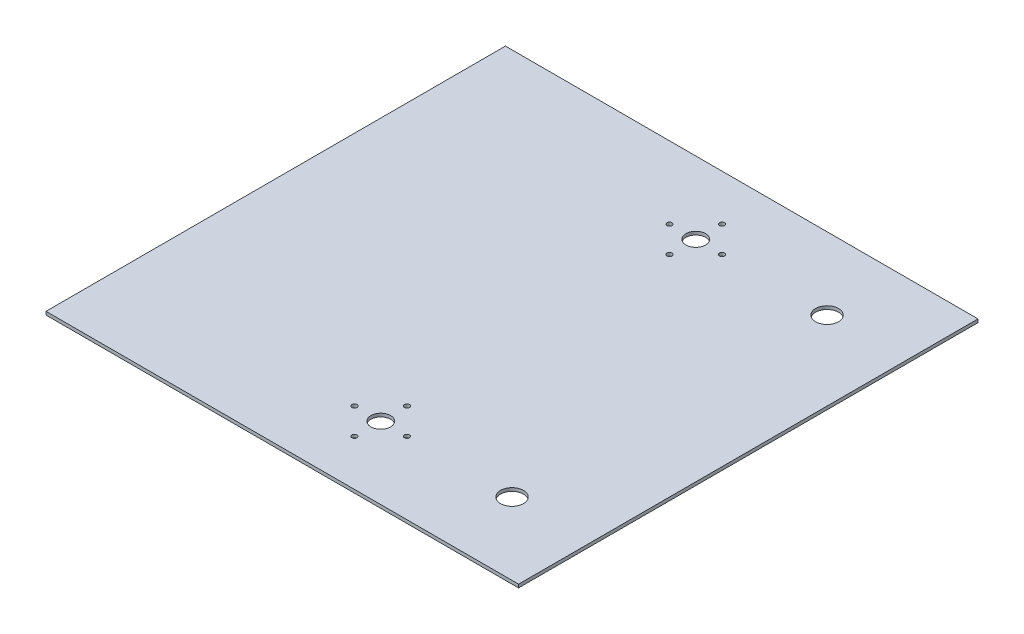
SolidWorks part; units mm, degrees
material "6061 Alloy"
ref_plane "Front Plane" through (0, 0, 0) normal (0, 0, 1) x (1, 0, 0)
ref_plane "Top Plane" through (0, 0, 0) normal (0, 1, 0) x (1, 0, 0)
ref_plane "Right Plane" through (0, 0, 0) normal (1, 0, 0) x (0, 0, -1)
sketch "Sketch1" plane through (0, 0, 0) normal (0, 1, 0) x (1, 0, 0)
  line L1 (228.6, -222.25) -> (-228.6, -222.25)
  line L2 (228.6, -222.25) -> (228.6, 222.25)
  line L3 (228.6, 222.25) -> (-228.6, 222.25)
  line L4 (-228.6, -222.25) -> (-228.6, 222.25)
  line L5 (228.6, -222.25) -> (-228.6, 222.25) construction
  line L6 (228.6, 222.25) -> (-228.6, -222.25) construction
  point P0 (0, 0)
  dimension "D1" = 457.2
  dimension "D2" = 444.5
extrude "Boss-Extrude1" add sketch "Sketch1" along normal blind 3.175
sketch "Sketch3" plane through (0, 3.175, 0) normal (0, 1, 0) x (1, 0, 0)
  arc A0 (34.925, -152.4) -> (15.875, -152.4) centre (25.4, -152.4) ccw construction
  arc A1 (15.875, -152.4) -> (34.925, -152.4) centre (25.4, -152.4) ccw construction
  arc A2 (34.925, -152.4) -> (15.875, -152.4) centre (25.4, -152.4) ccw
  arc A3 (15.875, -152.4) -> (34.925, -152.4) centre (25.4, -152.4) ccw
  arc A4 (34.925, 152.4) -> (15.875, 152.4) centre (25.4, 152.4) ccw construction
  arc A5 (15.875, 152.4) -> (34.925, 152.4) centre (25.4, 152.4) ccw construction
  arc A6 (34.925, 152.4) -> (15.875, 152.4) centre (25.4, 152.4) ccw
  arc A7 (15.875, 152.4) -> (34.925, 152.4) centre (25.4, 152.4) ccw
extrude "Cut-Extrude2" cut sketch "Sketch3" against normal through all
hole_wizard "#10 (0.1935) Diameter Hole1" positions "Sketch4" profile "Sketch5" hole size "#10" standard "ANSI Inch" end condition through all
sketch "Sketch4" plane through (0, 3.175, 0) normal (0, 1, 0) x (1, 0, 0)
  arc A0 (27.4193, -127) -> (23.3807, -127) centre (25.4, -127) ccw construction
  arc A1 (23.3807, -127) -> (27.4193, -127) centre (25.4, -127) ccw construction
  arc A2 (2.0193, -152.4) -> (-2.0193, -152.4) centre (0, -152.4) ccw construction
  arc A3 (-2.0193, -152.4) -> (2.0193, -152.4) centre (0, -152.4) ccw construction
  arc A4 (27.4193, -177.8) -> (23.3807, -177.8) centre (25.4, -177.8) ccw construction
  arc A5 (23.3807, -177.8) -> (27.4193, -177.8) centre (25.4, -177.8) ccw construction
  arc A6 (52.8193, -152.4) -> (48.7807, -152.4) centre (50.8, -152.4) ccw construction
  arc A7 (48.7807, -152.4) -> (52.8193, -152.4) centre (50.8, -152.4) ccw construction
  arc A8 (27.4193, -127) -> (23.3807, -127) centre (25.4, -127) ccw construction
  arc A9 (23.3807, -127) -> (27.4193, -127) centre (25.4, -127) ccw construction
  arc A10 (2.0193, -152.4) -> (-2.0193, -152.4) centre (0, -152.4) ccw construction
  arc A11 (-2.0193, -152.4) -> (2.0193, -152.4) centre (0, -152.4) ccw construction
  arc A12 (27.4193, -177.8) -> (23.3807, -177.8) centre (25.4, -177.8) ccw construction
  arc A13 (23.3807, -177.8) -> (27.4193, -177.8) centre (25.4, -177.8) ccw construction
  arc A14 (52.8193, -152.4) -> (48.7807, -152.4) centre (50.8, -152.4) ccw construction
  arc A15 (48.7807, -152.4) -> (52.8193, -152.4) centre (50.8, -152.4) ccw construction
  arc A16 (52.8193, 152.4) -> (48.7807, 152.4) centre (50.8, 152.4) ccw construction
  arc A17 (48.7807, 152.4) -> (52.8193, 152.4) centre (50.8, 152.4) ccw construction
  arc A18 (27.4193, 177.8) -> (23.3807, 177.8) centre (25.4, 177.8) ccw construction
  arc A19 (23.3807, 177.8) -> (27.4193, 177.8) centre (25.4, 177.8) ccw construction
  arc A20 (2.0193, 152.4) -> (-2.0193, 152.4) centre (0, 152.4) ccw construction
  arc A21 (-2.0193, 152.4) -> (2.0193, 152.4) centre (0, 152.4) ccw construction
  arc A22 (27.4193, 127) -> (23.3807, 127) centre (25.4, 127) ccw construction
  arc A23 (23.3807, 127) -> (27.4193, 127) centre (25.4, 127) ccw construction
  arc A24 (52.8193, 152.4) -> (48.7807, 152.4) centre (50.8, 152.4) ccw
  arc A25 (48.7807, 152.4) -> (52.8193, 152.4) centre (50.8, 152.4) ccw
  arc A26 (27.4193, 177.8) -> (23.3807, 177.8) centre (25.4, 177.8) ccw
  arc A27 (23.3807, 177.8) -> (27.4193, 177.8) centre (25.4, 177.8) ccw
  arc A28 (2.0193, 152.4) -> (-2.0193, 152.4) centre (0, 152.4) ccw
  arc A29 (-2.0193, 152.4) -> (2.0193, 152.4) centre (0, 152.4) ccw
  arc A30 (27.4193, 127) -> (23.3807, 127) centre (25.4, 127) ccw
  arc A31 (23.3807, 127) -> (27.4193, 127) centre (25.4, 127) ccw
  point P0 (25.4, -177.8)
  point P2 (0, -152.4)
  point P4 (25.4, -127)
  point P6 (50.8, -152.4)
  point P44 (25.4, 177.8)
  point P50 (0, 152.4)
  point P56 (25.4, 127)
  point P68 (50.8, 152.4)
  point P71 (50.8, 152.4)
sketch "Sketch5" plane through (25.4, 3.175, 177.8) normal (1, 0, 0) x (0, 0, 1)
  line L0 (0, 0) -> (0, 3.175)
  line L1 (0, 3.175) -> (2.4574, 3.175)
  line L2 (2.4574, 3.175) -> (2.4574, 0)
  line L5 (2.4574, 0) -> (0, 0)
  line L11 (0, -6.35) -> (0, 107.95) construction
  dimension "Thru Hole Dia." = 4.9149
  dimension "Thru Hole Depth" = 3.175
sketch "Sketch6" plane through (0, 3.175, 0) normal (0, 1, 0) x (1, 0, 0)
  line L0 (25.4, -114.3) -> (25.4, 114.3) construction
  line L1 (152.4, -152.4) -> (25.4, -152.4) construction
  line L2 (152.4, 152.4) -> (25.4, 152.4) construction
  circle A0 centre (25.4, -152.4) radius 38.1 construction
  circle A1 centre (25.4, 152.4) radius 38.1 construction
  circle A2 centre (152.4, -152.4) radius 38.1 construction
  circle A3 centre (152.4, 152.4) radius 38.1 construction
  dimension "D1" = 76.2
  dimension "D2" = 228.6
  dimension "D3" = 127
sketch "Sketch7" plane through (0, 3.175, 0) normal (0, 1, 0) x (1, 0, 0)
  circle A0 centre (152.4, -152.4) radius 11.1125
  circle A1 centre (152.4, 152.4) radius 11.1125
  dimension "D1" = 22.225
extrude "Cut-Extrude3" cut sketch "Sketch7" against normal through all
